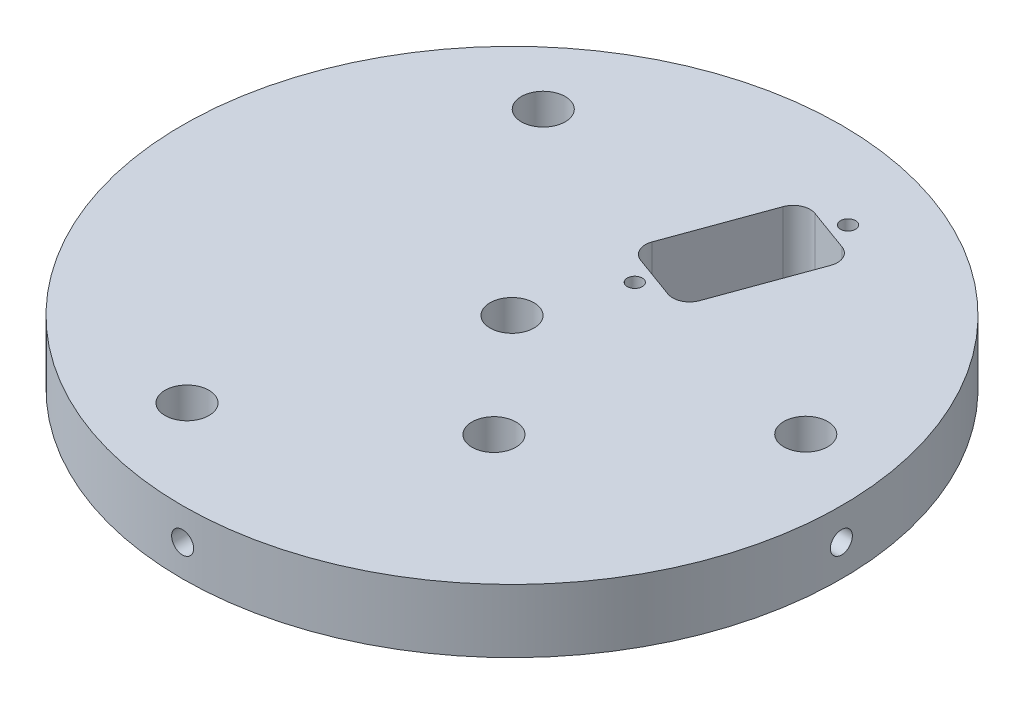
SolidWorks part; units mm, degrees
material "6061-T6 (SS)"
ref_plane "Front Plane" through (0, 0, 0) normal (0, 0, 1) x (1, 0, 0)
ref_plane "Top Plane" through (0, 0, 0) normal (0, 1, 0) x (1, 0, 0)
ref_plane "Right Plane" through (0, 0, 0) normal (1, 0, 0) x (0, 0, -1)
sketch "Sketch1" plane through (0, 0, 0) normal (0, 1, 0) x (1, 0, 0)
  line L0 (0, 0) -> (-50.3682, 60.0265)
  line L1 (0, 0) -> (50.3682, 60.0265)
  line L2 (0, 0) -> (0, 72.1431) construction
  circle A0 centre (0, 0) radius 78.359
  circle A1 centre (0, 0) radius 51.1048
  circle A2 centre (0, 0) radius 76.1746
  dimension "D1" = 156.718
  dimension "D2" = 102.2096
  dimension "D3" = 152.3492
  dimension "D4" = 80
extrude "Boss-Extrude1" add sketch "Sketch1" along normal blind 25.4 contours L2 A2 L1 A0 | L2 A1 L1 A2 | L2 A2 L1 A1 | L2 A0 L1 A2 | A2 L2 A1 L0 | A0 L2 A2 L0 | A2 L2 A0 L0 | A1 L2 A2 L0 region at (-22.4568, 0, 48.1587) region at (-40.1048, 0, -49.4238) region at (-33.0764, 0, 70.9325) region at (-48.8794, 0, -59.85)
ref_plane "Plane1" through (0, 12.7, 0) normal (0, 1, 0) x (1, 0, 0)
sketch "Sketch6" plane through (0, 25.4, 0) normal (0, 1, 0) x (1, 0, 0)
  circle A0 centre (0, 0) radius 49.5173
  dimension "D1" = 99.0346
extrude "Boss-Extrude5" add sketch "Sketch6" along normal blind 9.525
sketch "Sketch7" plane through (0, 0, 0) normal (0, -1, 0) x (1, 0, 0)
  circle A0 centre (0, 0) radius 49.5173
  dimension "D1" = 99.0346
extrude "Boss-Extrude6" add sketch "Sketch7" along normal blind 9.525
sketch "Sketch8" plane through (0, -9.525, 0) normal (0, -1, 0) x (1, 0, 0)
  circle A0 centre (0, 0) radius 46.99
  dimension "D1" = 93.98
ref_plane "Plane2" through (0, 0, -49.5173) normal (0, 0, -1) x (-1, 0, 0)
ref_plane "Plane5" through (0, 25.4, 0) normal (0, 1, 0) x (1, 0, 0)
ref_axis "Axis1" through (0, 0, 0) along (0, 1, 0)
ref_plane "Plane3" through (0, 34.925, 0) normal (0, 1, 0) x (1, 0, 0)
sketch "Sketch9" plane through (0, 34.925, 0) normal (0, 1, 0) x (1, 0, 0)
  line L0 (0, 0) -> (-26.8004, -73.6334) construction
  line L1 (0, 0) -> (32.0596, -38.2071) construction
  line L2 (0, 0) -> (0, -86.0416) construction
  circle A0 centre (0, 0) radius 3.3
  circle A1 centre (-13.031, -35.8023) radius 3.3
  circle A4 centre (14.1499, -16.8632) radius 3.3
  circle A5 centre (-24.4902, 29.1863) radius 3.3
  circle A6 centre (37.5212, 6.616) radius 3.3
  point P15 (-1.3039, -1.0954)
  point P18 (0, 0)
  dimension "D1" = 6.6
  dimension "D2" = 6.6
  dimension "D6" = 6.6
  dimension "D3" = 38.1
  dimension "D4" = 60
  dimension "D7" = 22.0133
  dimension "D8" = 20
extrude "Cut-Extrude6" cut sketch "Sketch9" against normal through all
sketch "Sketch10" plane through (0, 25.4, 0) normal (0, 1, 0) x (1, 0, 0)
  circle A0 centre (0, 0) radius 82.3228
extrude "Cut-Extrude7" cut sketch "Sketch10" against normal through all
hole_wizard "Tap Drill for #4-40 Tap1" positions "Sketch12" profile "Sketch13" hole size "#4-40" standard "ANSI Inch" end condition through all
sketch "Sketch12" plane through (0, 34.925, 0) normal (0, 1, 0) x (1, 0, 0)
  line L0 (0, 0) -> (18.0627, 49.6269) construction
  line L2 (0, 0) -> (-24.4902, 29.1863) construction
  circle A0 centre (0, 0) radius 14.3933 construction
  point P0 (4.9228, 13.5253)
  point P2 (13.4733, 37.0176)
  dimension "D3" = 28.7867
  dimension "D1" = 60
  dimension "D2" = 25
sketch "Sketch13" plane through (4.9228, 34.925, -13.5253) normal (1, 0, 0) x (0, 0, 1)
  line L0 (0, 0) -> (0, 9.525)
  line L1 (0, 9.525) -> (1.1303, 9.525)
  line L2 (1.1303, 9.525) -> (1.1303, 0)
  line L5 (1.1303, 0) -> (0, 0)
  line L11 (0, -6.35) -> (0, 107.95) construction
  dimension "Thru Hole Dia." = 2.2606
  dimension "Thru Hole Depth" = 9.525
sketch "Sketch14" plane through (0, 34.925, 0) normal (0, 1, 0) x (1, 0, 0)
  line L0 (4.9228, 13.5253) -> (13.4733, 37.0176) construction
  line L1 (12.1824, 16.0187) -> (17.4317, 30.4411)
  line L2 (8.9269, 14.5007) -> (2.4825, 16.8462)
  line L3 (15.9137, 33.6967) -> (9.4692, 36.0423)
  line L4 (0.9644, 20.1018) -> (6.2137, 34.5242)
  arc A0 (17.4317, 30.4411) -> (15.9137, 33.6967) centre (15.0449, 31.3099) ccw
  arc A1 (9.4692, 36.0423) -> (6.2137, 34.5242) centre (8.6005, 33.6555) ccw
  arc A2 (8.9269, 14.5007) -> (12.1824, 16.0187) centre (9.7956, 16.8875) ccw
  arc A3 (2.4825, 16.8462) -> (0.9644, 20.1018) centre (3.3512, 19.2331) cw
  point P0 (5.7047, 15.6734)
  dimension "D4" = 2.54
  dimension "D5" = 2.54
  dimension "D2" = 2.286
  dimension "D3" = 11.938
extrude "Cut-Extrude9" cut sketch "Sketch14" against normal through all
ref_plane "Plane6" through (49.5173, 0, 0) normal (1, 0, 0) x (0, 0, -1)
hole_wizard "Tap Drill for M4x0.7 Tap1" positions "Sketch16" profile "Sketch17" hole size "M4x0.7" standard "ANSI Metric"
sketch "Sketch16" plane through (49.5173, 0, 0) normal (1, 0, 0) x (0, 0, -1)
  line L1 (49.5173, 34.925) -> (-49.5173, 34.925) construction
  point P0 (0, 30.1625)
  dimension "D1" = 4.7625
sketch "Sketch17" plane through (49.5173, 30.1625, 0) normal (0, 1, 0) x (0, 0, -1)
  line L0 (0, 0) -> (0, 10.6434)
  line L1 (0, 10.6434) -> (1.65, 9.652)
  line L2 (1.65, 9.652) -> (1.65, 0)
  line L5 (1.65, 0) -> (0, 0)
  line L10 (0, 10.6434) -> (-1.65, 9.652) construction
  line L11 (0, -6.35) -> (0, 107.95) construction
  dimension "Hole Dia." = 3.3
  dimension "Hole Depth" = 9.652
  dimension "Drill Angle" = 118
pattern_circular "CirPattern1" count 4 over 360 about axis through (0, 34.925, 0) along (0, 1, 0) of "Tap Drill for M4x0.7 Tap1"
equation "\"AB_Coupler_OD_Length\"= 1in"
equation "\"AB_Coupling_Section_Length\"= 0.375in"
equation "\"AB_Coupler_Length\"= \"AB_Coupler_OD_Length\" + \"AB_Coupling_Section_Length\" * 2"
equation "\"Cutout_Angle\" = 60"
equation "\"AB_Coupler_Num_Screws\"= 4"
equation "\"Num_Cutouts\" = 4"
equation "\"AB_Coupler_OD\"= 4.024in"
equation "\"AB_Coupler_ID\"= 3.7in"
equation "\"AB_Coupler_Surface_Diameter\"= 3.899in"
equation "\"D2@Sketch1\"= \"Body_Tube_OD\""
equation "\"AB_Coupling_Screw_Diameter\"= 0.1065in"
equation "\"Aft_Section_Length\" = 32in"
equation "\"Mid_Coupler_Length\" = 12in"
equation "\"Lead_Screw_Dist\" = 2in"
equation "\"Lead_Screw_Diam\" = 0.375in"
equation "\"Lead_Screw_Length\" = \"Mid_Coupler_Length\" + 2*0.375in + 2*0.5in"
equation "\"Paddle_Pin_Offset\" = 0.25in"
equation "\"Paddle_Pin_Radius\" = 2.25*2/3in"
equation "\"D1@Sketch6\"=\"AB_Coupler_Surface_Diameter\""
equation "\"D1@Boss-Extrude5\"=\"AB_Coupling_Section_Length\""
equation "\"D1@Sketch7\"=\"AB_Coupler_Surface_Diameter\""
equation "\"D1@Boss-Extrude6\"=\"AB_Coupling_Section_Length\""
equation "\"D1@Sketch8\"=\"AB_Coupler_ID\""
equation "\"D3@Sketch9\"=\"Paddle_Pin_Radius\""
equation "\"Motor_OD\" = 54.4mm"
equation "\"AB_Paddle_Height\" = 0.375in"
equation "\"AB_Central_Bushing_Length\" = 0.75in"
equation "\"Paddle_Gear_OD\" = 3.2in"
equation "\"Fwd_BKHD_From_Top\" = 18in"
equation "\"Fin_Thickness\" = 0.118in"
equation "\"DB9_Hole_Dist\" = 25mm"
equation "\"D2@Sketch12\"=\"DB9_Hole_Dist\""
equation "\"Drive_Gear_OD\" = 1.7*2/3in"
equation "\"D3@Sketch12\"=\"Drive_Gear_OD\""
equation "\"DB9_Relief_Width\" = 0.47in"
equation "\"D3@Sketch14\"=\"DB9_Relief_Width\""
equation "\"DB9_Relief_Hole_Offset\" = 0.09in"
equation "\"D2@Sketch14\"=\"DB9_Relief_Hole_Offset\""
equation "\"D1@Sketch14\"=\"DB9_Relief_Hole_Offset\""
equation "\"Airbrakes_Wire_Hole_Dia\" = 0.25in"
equation "\"Airbrakes_Wire_Hole_Dist\" = 1.1in"
equation "\"Servo_Gear_Offset\" = 0.5in"
equation "\"Motor_Length\" = 401mm"
equation "\"Body_Tube_OD\"= 4.024in"
equation "\"Body_Tube_ID\"= 3.90in"
equation "\"Coupler_OD\" = 3.899in"
equation "\"Coupler_ID\" = 3.755in"
equation "\"Fwd_Section_Length\" = 20in"
equation "\"Mid_Section_Length\" = 4in"
equation "\"Aft_Upper_Tube_Length\" = 10in"
equation "\"Aft_Lower_Tube_Length\" = 18in"
equation "\"Nosecone_Coupler_Length\" = 5in"
equation "\"Avionics_Bulkhead_Thickness\" = 0.25in"
equation "\"Avionics_Bulkhead_Lip\" = 0.125in"
equation "\"Avionics_Board_Length\" = \"Mid_Coupler_Length\" - 2*\"Avionics_Bulkhead_Lip\""
equation "\"Lead_Screw_Hole_Diam\" = 0.386in"
equation "\"Centering_Ring_Cutout_Dia\"=1.5in"
equation "\"D7@Sketch9\"=\"Drive_Gear_OD\"/2+.3"
equation "\"D1@Sketch16\"=.375/2"
